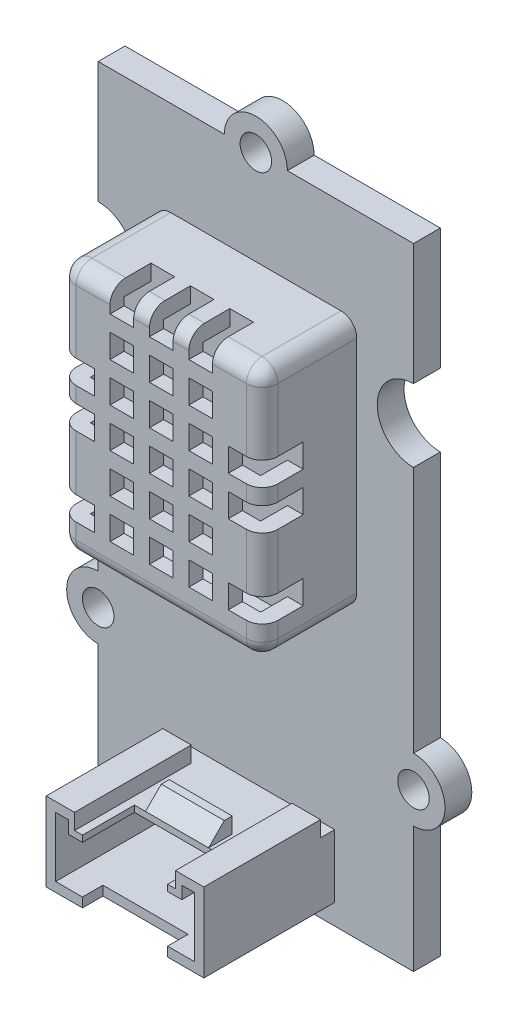
SolidWorks part; units mm, degrees
ref_plane "Plan de face" through (0, 0, 0) normal (0, 0, 1) x (1, 0, 0)
ref_plane "Plan de dessus" through (0, 0, 0) normal (0, 1, 0) x (1, 0, 0)
ref_plane "Plan de droite" through (0, 0, 0) normal (1, 0, 0) x (0, 0, -1)
sketch "Esquisse1" plane through (0, 0, 0) normal (0, 0, 1) x (1, 0, 0)
  line L0 (-4.3295, 15.3409) -> (3.6705, 15.3409)
  line L1 (-16.3295, 15.3409) -> (-8.3295, 15.3409)
  line L2 (-16.3295, 15.3409) -> (-16.3295, 7.6409)
  line L3 (-16.3295, -24.6591) -> (-8.6295, -24.6591)
  line L4 (3.6705, 15.3409) -> (3.6705, 7.6409)
  line L5 (-4.0295, -24.6591) -> (3.6705, -24.6591)
  line L6 (-30.4204, -14.6591) -> (11.8523, -14.6591) construction
  line L7 (-28.1477, 5.3409) -> (11.8523, 5.3409) construction
  line L8 (-16.3295, 3.0409) -> (-16.3295, -12.6591)
  line L9 (3.6705, 3.0409) -> (3.6705, -12.6591)
  line L10 (3.6705, -16.6591) -> (3.6705, -24.6591)
  line L11 (-16.3295, -16.6591) -> (-16.3295, -24.6591)
  arc A0 (-4.3295, 15.3409) -> (-8.3295, 15.3409) centre (-6.3295, 15.3409) ccw
  arc A1 (-4.0295, -24.6591) -> (-8.6295, -24.6591) centre (-6.3295, -24.6591) ccw
  arc A2 (-16.3295, 3.0409) -> (-16.3295, 7.6409) centre (-16.3295, 5.3409) ccw
  arc A3 (3.6705, 7.6409) -> (3.6705, 3.0409) centre (3.6705, 5.3409) ccw
  arc A4 (-16.3295, -12.6591) -> (-16.3295, -16.6591) centre (-16.3295, -14.6591) ccw
  arc A5 (3.6705, -16.6591) -> (3.6705, -12.6591) centre (3.6705, -14.6591) ccw
  point P14 (-12.3295, 15.3409)
  dimension "D3" = 10
  dimension "D1" = 20
  dimension "D2" = 40
  dimension "D4" = 10
extrude "Boss.-Extru.1" add sketch "Esquisse1" along normal blind 1.7
sketch "Esquisse2" plane through (0, 0, 1.7) normal (0, 0, 1) x (1, 0, 0)
  circle A0 centre (-6.3295, 15.3409) radius 1
  circle A1 centre (-16.3295, -14.6591) radius 1
  circle A2 centre (3.6705, -14.6591) radius 1
extrude "Enlèv. mat.-Extru.1" cut sketch "Esquisse2" against normal blind 1.7
sketch "Esquisse3" plane through (0, 0, 1.7) normal (0, 0, 1) x (1, 0, 0)
  line L0 (-16.3295, -16.6591) -> (-16.3295, -24.6591) construction
  line L1 (-11.3295, -18.3591) -> (-1.3295, -18.3591)
  line L2 (-11.3295, -18.3591) -> (-11.3295, -23.3591)
  line L3 (-11.3295, -23.3591) -> (-1.3295, -23.3591)
  line L4 (-1.3295, -18.3591) -> (-1.3295, -23.3591)
  line L5 (-16.3295, -24.6591) -> (-8.6295, -24.6591) construction
  dimension "D1" = 10
  dimension "D2" = 5
  dimension "D3" = 5
  dimension "D4" = 1.3
extrude "Boss.-Extru.2" add sketch "Esquisse3" along normal blind 8.3
sketch "Esquisse4" plane through (0, -18.3591, 0) normal (0, 1, 0) x (1, 0, 0)
  line L0 (-11.3295, -1.7) -> (-1.3295, -1.7)
  line L1 (-1.3295, -1.7) -> (-1.3295, -2.6)
  line L2 (-1.3295, -10) -> (-1.3295, -1.7) construction
  line L3 (-1.3295, -2.6) -> (-3.1295, -2.6)
  line L4 (-3.1295, -2.6) -> (-3.1295, -10)
  line L5 (-1.3295, -10) -> (-11.3295, -10) construction
  line L6 (-11.3295, -1.7) -> (-11.3295, -2.6)
  line L7 (-11.3295, -10) -> (-11.3295, -1.7) construction
  line L8 (-11.3295, -2.6) -> (-9.5295, -2.6)
  line L9 (-9.5295, -2.6) -> (-9.5295, -10)
  line L10 (-9.5295, -10) -> (-3.1295, -10)
  line L11 (-6.3295, -10) -> (-6.3295, -3.6134) construction
  line L12 (-8.3295, -5.2) -> (-4.3295, -5.2)
  line L13 (-8.3295, -5.2) -> (-8.3295, -6.7)
  line L14 (-8.3295, -6.7) -> (-4.3295, -6.7)
  line L15 (-4.3295, -5.2) -> (-4.3295, -6.7)
  dimension "D1" = 3.3
  dimension "D2" = 1.5
  dimension "D3" = 4
  dimension "D4" = 2
  dimension "D5" = 1.8
extrude "Enlèv. mat.-Extru.2" cut sketch "Esquisse4" against normal blind 1
chamfer "Chanfrein1" distance 1 angle 45 1 edges at (-6.3295, -18.3591, 6.7)
sketch "Esquisse5" plane through (0, -19.3591, 0) normal (0, 1, 0) x (1, 0, 0)
  line L0 (-9.5295, -10) -> (-3.1295, -10) construction
  line L1 (-9.0295, -10) -> (-3.6295, -10)
  line L2 (-9.0295, -10) -> (-9.0295, -6.699)
  line L3 (-9.0295, -6.699) -> (-3.6295, -6.699)
  line L4 (-3.6295, -10) -> (-3.6295, -6.699)
  line L5 (-6.3295, -10) -> (-6.3295, -3.965) construction
  line L6 (-8.3295, -5.2) -> (-8.3295, -6.7) construction
  point P10 (-8.3295, -5.95)
  dimension "D1" = 5.4
  dimension "D2" = 2.7
  dimension "D3" = 0.7
extrude "Enlèv. mat.-Extru.3" cut sketch "Esquisse5" against normal blind 1
sketch "Esquisse6" plane through (0, -20.3591, 0) normal (0, 1, 0) x (1, 0, 0)
  line L0 (-3.6295, -10) -> (-3.6295, -6.699) construction
  line L1 (-9.0295, -10) -> (-3.6295, -10)
  line L2 (-9.0295, -10) -> (-9.0295, -8.7)
  line L3 (-9.0295, -8.7) -> (-3.6295, -8.7)
  line L4 (-3.6295, -10) -> (-3.6295, -8.7)
  dimension "D1" = 1.3
extrude "Enlèv. mat.-Extru.4" cut sketch "Esquisse6" against normal blind 21
sketch "Esquisse7" plane through (0, 0, 10) normal (0, 0, 1) x (1, 0, 0)
  line L0 (-11.3295, -18.3591) -> (-11.3295, -23.3591) construction
  line L1 (-9.9295, -19.7591) -> (-2.7295, -19.7591)
  line L2 (-10.7295, -19.7591) -> (-10.7295, -22.7591)
  line L3 (-10.7295, -22.7591) -> (-1.9295, -22.7591)
  line L4 (-1.9295, -19.7591) -> (-1.9295, -22.7591)
  line L5 (-11.3295, -23.3591) -> (-9.0295, -23.3591) construction
  line L6 (-1.3295, -23.3591) -> (-1.3295, -18.3591) construction
  line L7 (-10.7295, -19.7591) -> (-10.7295, -18.9591)
  line L8 (-10.7295, -18.9591) -> (-9.9295, -18.9591)
  line L9 (-9.9295, -18.9591) -> (-9.9295, -19.7591)
  line L10 (-1.9295, -19.7591) -> (-1.9295, -18.9591)
  line L11 (-1.9295, -18.9591) -> (-2.7295, -18.9591)
  line L12 (-2.7295, -18.9591) -> (-2.7295, -19.7591)
  dimension "D1" = 0.6
  dimension "D2" = 0.6
  dimension "D3" = 0.6
  dimension "D4" = 3
extrude "Enlèv. mat.-Extru.5" cut sketch "Esquisse7" against normal blind 7
sketch "Esquisse8" plane through (0, 0, 1.7) normal (0, 0, 1) x (1, 0, 0)
  line L0 (-16.3295, 3.0409) -> (-16.3295, -12.6591) construction
  line L1 (-11.7295, 9.3409) -> (-0.9295, 9.3409)
  line L2 (-12.7295, 8.3409) -> (-12.7295, -5.6591)
  line L3 (-11.7295, -6.6591) -> (-0.9295, -6.6591)
  line L4 (0.0705, 8.3409) -> (0.0705, -5.6591)
  circle A0 centre (-6.3295, 15.3409) radius 1 construction
  arc A1 (-12.7295, -5.6591) -> (-11.7295, -6.6591) centre (-11.7295, -5.6591) ccw
  arc A2 (-0.9295, -6.6591) -> (0.0705, -5.6591) centre (-0.9295, -5.6591) ccw
  arc A3 (-0.9295, 9.3409) -> (0.0705, 8.3409) centre (-0.9295, 8.3409) cw
  arc A4 (-11.7295, 9.3409) -> (-12.7295, 8.3409) centre (-11.7295, 8.3409) ccw
  point P10 (-12.7295, -6.6591)
  point P15 (0.0705, 9.3409)
  point P18 (-12.7295, 9.3409)
  dimension "D5" = 1
  dimension "D1" = 6
  dimension "D2" = 12.8
  dimension "D3" = 16
  dimension "D4" = 3.6
extrude "Boss.-Extru.3" add sketch "Esquisse8" along normal blind 6
fillet "Congé1" radius 1 8 edges at (-12.7295, 1.3409, 7.7) (-12.4366, 9.048, 7.7) (-6.3295, 9.3409, 7.7) (-0.2224, 9.048, 7.7) (0.0705, 1.3409, 7.7) (-0.2224, -6.3662, 7.7) (-6.3295, -6.6591, 7.7) (-12.4366, -6.3662, 7.7)
sketch "Esquisse9" plane through (0, 0, 7.7) normal (0, 0, 1) x (1, 0, 0)
  line L0 (-6.3295, -6.6591) -> (-6.3295, 10.9744) construction
  line L1 (-11.7295, -6.6591) -> (-0.9295, -6.6591) construction
  line L2 (-0.9295, 9.3409) -> (-11.7295, 9.3409) construction
  line L3 (-7.0795, 9.3409) -> (-5.5795, 9.3409)
  line L4 (-7.0795, 9.3409) -> (-7.0795, 7.8409)
  line L5 (-7.0795, 7.8409) -> (-5.5795, 7.8409)
  line L6 (-5.5795, 9.3409) -> (-5.5795, 7.8409)
  line L7 (-4.5795, 9.3409) -> (-3.0795, 9.3409)
  line L8 (-4.5795, 9.3409) -> (-4.5795, 7.8409)
  line L9 (-4.5795, 7.8409) -> (-3.0795, 7.8409)
  line L10 (-3.0795, 9.3409) -> (-3.0795, 7.8409)
  line L15 (-4.5795, 6.8409) -> (-3.0795, 6.8409)
  line L16 (-4.5795, 6.8409) -> (-4.5795, 5.3409)
  line L17 (-4.5795, 5.3409) -> (-3.0795, 5.3409)
  line L18 (-3.0795, 6.8409) -> (-3.0795, 5.3409)
  line L23 (-4.5795, 4.3409) -> (-3.0795, 4.3409)
  line L24 (-4.5795, 4.3409) -> (-4.5795, 2.8409)
  line L25 (-4.5795, 2.8409) -> (-3.0795, 2.8409)
  line L26 (-3.0795, 4.3409) -> (-3.0795, 2.8409)
  line L27 (-2.0795, 4.3409) -> (-0.5795, 4.3409)
  line L28 (-2.0795, 4.3409) -> (-2.0795, 2.8409)
  line L29 (-2.0795, 2.8409) -> (-0.5795, 2.8409)
  line L31 (-4.5795, 1.8409) -> (-3.0795, 1.8409)
  line L32 (-4.5795, 1.8409) -> (-4.5795, 0.3409)
  line L33 (-4.5795, 0.3409) -> (-3.0795, 0.3409)
  line L34 (-3.0795, 1.8409) -> (-3.0795, 0.3409)
  line L35 (-2.0795, 1.8409) -> (-0.5795, 1.8409)
  line L36 (-2.0795, 1.8409) -> (-2.0795, 0.3409)
  line L37 (-2.0795, 0.3409) -> (-0.5795, 0.3409)
  line L39 (-4.5795, -0.6591) -> (-3.0795, -0.6591)
  line L40 (-4.5795, -0.6591) -> (-4.5795, -2.1591)
  line L41 (-4.5795, -2.1591) -> (-3.0795, -2.1591)
  line L42 (-3.0795, -0.6591) -> (-3.0795, -2.1591)
  line L47 (-4.5795, -3.1591) -> (-3.0795, -3.1591)
  line L48 (-4.5795, -3.1591) -> (-4.5795, -4.6591)
  line L49 (-4.5795, -4.6591) -> (-3.0795, -4.6591)
  line L50 (-3.0795, -3.1591) -> (-3.0795, -4.6591)
  line L51 (-2.0795, -3.1591) -> (-0.5795, -3.1591)
  line L52 (-2.0795, -3.1591) -> (-2.0795, -4.6591)
  line L53 (-2.0795, -4.6591) -> (-0.5795, -4.6591)
  line L55 (-7.0795, 6.8409) -> (-5.5795, 6.8409)
  line L56 (-7.0795, 6.8409) -> (-7.0795, 5.3409)
  line L57 (-7.0795, 5.3409) -> (-5.5795, 5.3409)
  line L58 (-5.5795, 6.8409) -> (-5.5795, 5.3409)
  line L59 (-7.0795, 4.3409) -> (-5.5795, 4.3409)
  line L60 (-7.0795, 4.3409) -> (-7.0795, 2.8409)
  line L61 (-7.0795, 2.8409) -> (-5.5795, 2.8409)
  line L62 (-5.5795, 4.3409) -> (-5.5795, 2.8409)
  line L63 (-7.0795, 1.8409) -> (-5.5795, 1.8409)
  line L64 (-7.0795, 1.8409) -> (-7.0795, 0.3409)
  line L65 (-7.0795, 0.3409) -> (-5.5795, 0.3409)
  line L66 (-5.5795, 1.8409) -> (-5.5795, 0.3409)
  line L67 (-7.0795, -0.6591) -> (-5.5795, -0.6591)
  line L68 (-7.0795, -0.6591) -> (-7.0795, -2.1591)
  line L69 (-7.0795, -2.1591) -> (-5.5795, -2.1591)
  line L70 (-5.5795, -0.6591) -> (-5.5795, -2.1591)
  line L71 (-7.0795, -3.1591) -> (-5.5795, -3.1591)
  line L72 (-7.0795, -3.1591) -> (-7.0795, -4.6591)
  line L73 (-7.0795, -4.6591) -> (-5.5795, -4.6591)
  line L74 (-5.5795, -3.1591) -> (-5.5795, -4.6591)
  line L75 (-9.5795, 9.3409) -> (-8.0795, 9.3409)
  line L76 (-9.5795, 9.3409) -> (-9.5795, 7.8409)
  line L77 (-9.5795, 7.8409) -> (-8.0795, 7.8409)
  line L78 (-8.0795, 9.3409) -> (-8.0795, 7.8409)
  line L79 (-9.5795, 6.8409) -> (-8.0795, 6.8409)
  line L80 (-9.5795, 6.8409) -> (-9.5795, 5.3409)
  line L81 (-9.5795, 5.3409) -> (-8.0795, 5.3409)
  line L82 (-8.0795, 6.8409) -> (-8.0795, 5.3409)
  line L83 (-9.5795, 4.3409) -> (-8.0795, 4.3409)
  line L84 (-9.5795, 4.3409) -> (-9.5795, 2.8409)
  line L85 (-9.5795, 2.8409) -> (-8.0795, 2.8409)
  line L86 (-8.0795, 4.3409) -> (-8.0795, 2.8409)
  line L87 (-9.5795, 1.8409) -> (-8.0795, 1.8409)
  line L88 (-9.5795, 1.8409) -> (-9.5795, 0.3409)
  line L89 (-9.5795, 0.3409) -> (-8.0795, 0.3409)
  line L90 (-8.0795, 1.8409) -> (-8.0795, 0.3409)
  line L91 (-9.5795, -0.6591) -> (-8.0795, -0.6591)
  line L92 (-9.5795, -0.6591) -> (-9.5795, -2.1591)
  line L93 (-9.5795, -2.1591) -> (-8.0795, -2.1591)
  line L94 (-8.0795, -0.6591) -> (-8.0795, -2.1591)
  line L95 (-9.5795, -3.1591) -> (-8.0795, -3.1591)
  line L96 (-9.5795, -3.1591) -> (-9.5795, -4.6591)
  line L97 (-9.5795, -4.6591) -> (-8.0795, -4.6591)
  line L98 (-8.0795, -3.1591) -> (-8.0795, -4.6591)
  line L107 (-12.0795, 4.3409) -> (-10.5795, 4.3409)
  line L109 (-12.0795, 2.8409) -> (-10.5795, 2.8409)
  line L110 (-10.5795, 4.3409) -> (-10.5795, 2.8409)
  line L111 (-12.0795, 1.8409) -> (-10.5795, 1.8409)
  line L113 (-12.0795, 0.3409) -> (-10.5795, 0.3409)
  line L114 (-10.5795, 1.8409) -> (-10.5795, 0.3409)
  line L119 (-12.0795, -3.1591) -> (-10.5795, -3.1591)
  line L121 (-12.0795, -4.6591) -> (-10.5795, -4.6591)
  line L122 (-10.5795, -3.1591) -> (-10.5795, -4.6591)
  line L123 (-12.0795, 9.3409) -> (-10.5795, 9.3409) [skipped]
  line L124 (-12.0795, 9.3409) -> (-12.0795, 7.8409) [skipped]
  line L125 (-12.0795, 7.8409) -> (-10.5795, 7.8409) [skipped]
  line L126 (-10.5795, 9.3409) -> (-10.5795, 7.8409) [skipped]
  line L127 (-12.0795, 6.8409) -> (-10.5795, 6.8409) [skipped]
  line L128 (-12.0795, 6.8409) -> (-12.0795, 5.3409) [skipped]
  line L129 (-12.0795, 5.3409) -> (-10.5795, 5.3409) [skipped]
  line L130 (-10.5795, 6.8409) -> (-10.5795, 5.3409) [skipped]
  line L131 (-2.0795, 9.3409) -> (-0.5795, 9.3409) [skipped]
  line L132 (-2.0795, 9.3409) -> (-2.0795, 7.8409) [skipped]
  line L133 (-2.0795, 7.8409) -> (-0.5795, 7.8409) [skipped]
  line L134 (-0.5795, 9.3409) -> (-0.5795, 7.8409) [skipped]
  line L135 (-2.0795, 6.8409) -> (-0.5795, 6.8409) [skipped]
  line L136 (-2.0795, 6.8409) -> (-2.0795, 5.3409) [skipped]
  line L137 (-2.0795, 5.3409) -> (-0.5795, 5.3409) [skipped]
  line L138 (-0.5795, 6.8409) -> (-0.5795, 5.3409) [skipped]
  line L139 (-12.0795, -0.6591) -> (-10.5795, -0.6591) [skipped]
  line L140 (-12.0795, -0.6591) -> (-12.0795, -2.1591) [skipped]
  line L141 (-12.0795, -2.1591) -> (-10.5795, -2.1591) [skipped]
  line L142 (-10.5795, -0.6591) -> (-10.5795, -2.1591) [skipped]
  line L143 (-2.0795, -0.6591) -> (-0.5795, -0.6591) [skipped]
  line L144 (-2.0795, -0.6591) -> (-2.0795, -2.1591) [skipped]
  line L145 (-2.0795, -2.1591) -> (-0.5795, -2.1591) [skipped]
  line L146 (-0.5795, -0.6591) -> (-0.5795, -2.1591) [skipped]
  line L147 (-12.0795, 4.3409) -> (-12.7295, 4.3409)
  line L148 (-12.7295, 8.3409) -> (-12.7295, -5.6591) construction
  line L149 (-12.7295, 4.3409) -> (-12.7295, 2.8409)
  line L150 (-12.0795, 1.8409) -> (-12.7295, 1.8409)
  line L151 (-12.7295, 1.8409) -> (-12.7295, 0.3409)
  line L152 (-12.0795, -3.1591) -> (-12.7295, -3.1591)
  line L153 (-12.7295, -3.1591) -> (-12.7295, -4.6591)
  line L154 (-0.5795, 4.3409) -> (0.0705, 4.3409)
  line L155 (0.0705, -5.6591) -> (0.0705, 8.3409) construction
  line L156 (0.0705, 4.3409) -> (0.0705, 2.8409)
  line L157 (-0.5795, 1.8409) -> (0.0705, 1.8409)
  line L158 (0.0705, 1.8409) -> (0.0705, 0.3409)
  line L159 (-0.5795, 0.3409) -> (0.0705, 0.3409)
  line L164 (-0.5795, 2.8409) -> (0.0705, 2.8409)
  line L165 (-12.0795, 4.3409) -> (-12.0795, 2.8409) [skipped]
  line L166 (-12.0795, 1.8409) -> (-12.0795, 0.3409) [skipped]
  line L167 (-12.0795, -3.1591) -> (-12.0795, -4.6591) [skipped]
  line L168 (-0.5795, -3.1591) -> (-0.5795, -4.6591) [skipped]
  line L169 (-0.5795, 1.8409) -> (-0.5795, 0.3409) [skipped]
  line L170 (-0.5795, 4.3409) -> (-0.5795, 2.8409) [skipped]
  line L171 (-12.7295, -4.6591) -> (-12.0795, -4.6591)
  line L172 (-12.7295, 0.3409) -> (-12.0795, 0.3409)
  line L173 (-12.7295, 2.8409) -> (-12.0795, 2.8409)
  line L174 (-0.5795, -3.1591) -> (0.0705, -3.1591)
  line L175 (0.0705, -3.1591) -> (0.0705, -4.6591)
  line L176 (0.0705, -4.6591) -> (-0.5795, -4.6591)
  dimension "D1" = 3
  dimension "D2" = 1.5
  dimension "D4" = 6
extrude "Enlèv. mat.-Extru.6" cut sketch "Esquisse9" against normal blind 2.6
sketch "Esquisse10" plane through (0, 0, 5.1) normal (0, 0, 1) x (1, 0, 0)
  line L1 (-0.9295, -5.6591) -> (-11.7295, -5.6591)
  line L2 (-0.9295, -5.6591) -> (-0.9295, 8.3409)
  line L3 (-0.9295, 8.3409) -> (-11.7295, 8.3409)
  line L4 (-11.7295, -5.6591) -> (-11.7295, 8.3409)
extrude "Enlèv. mat.-Extru.8" cut sketch "Esquisse10" along normal blind 1.7
